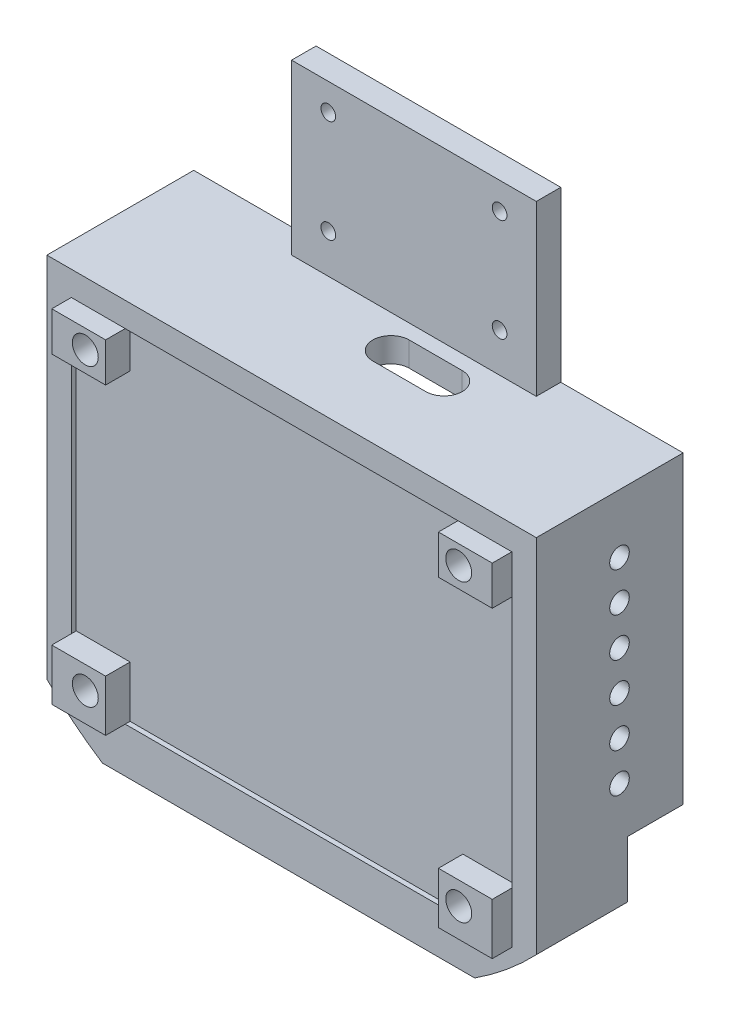
SolidWorks part; units mm, degrees
material "PLA"
ref_plane "Plano frontal" through (0, 0, 0) normal (0, 0, 1) x (1, 0, 0)
ref_plane "Plano superior" through (0, 0, 0) normal (0, 1, 0) x (1, 0, 0)
ref_plane "Plano direito" through (0, 0, 0) normal (1, 0, 0) x (0, 0, -1)
other "pla"
sketch "Esboço1" plane through (0, 0, 0) normal (0, 0, 1) x (1, 0, 0)
  line L6 (-49.3816, -49.6131) -> (-49.3816, 49.6131)
  line L8 (50.6184, -48.3506) -> (50.6184, 48.3506)
  arc A0 (-49.3816, -49.6131) -> (50.6184, -48.3506) centre (0, 0) ccw
  arc A1 (50.6184, 48.3506) -> (-49.3816, 49.6131) centre (0, 0) ccw
  point P0 (0, 0)
  dimension "D1" = 100
extrude "Ressalto-extrusão1" add sketch "Esboço1" along normal blind 30
sketch "Esboço10" plane through (0, 0, 30) normal (0, 0, 1) x (1, 0, 0)
  line L1 (-56.0991, 25.4453) -> (56.0991, 25.4453)
  line L2 (-56.0991, 25.4453) -> (-56.0991, 73.7415)
  line L3 (-56.0991, 73.7415) -> (56.0991, 73.7415)
  line L4 (56.0991, 25.4453) -> (56.0991, 73.7415)
  line L5 (-56.0991, 25.4453) -> (56.0991, 73.7415) construction
  line L6 (-56.0991, 73.7415) -> (56.0991, 25.4453) construction
  point P0 (0, 49.5934)
extrude "Corte-extrusão6" cut sketch "Esboço10" against normal blind 25
sketch "Esboço12" plane through (0, 0, 5) normal (0, 0, 1) x (1, 0, 0)
  line L0 (-24.3816, 25.4453) -> (-24.3816, 72.1449)
  line L1 (-49.3816, 25.4453) -> (50.6184, 25.4453) construction
  line L3 (25.6184, 72.1449) -> (25.6184, 25.4453)
  line L5 (50.6184, 48.3506) -> (50.6184, 25.4453) construction
  line L6 (-49.3816, 25.4453) -> (-49.3816, 49.6131) construction
  line L7 (-38.033, -58.7664) -> (38.033, -58.7664)
  line L8 (38.033, -58.7664) -> (38.033, -75.3889)
  line L9 (38.033, -75.3889) -> (-38.033, -75.3889)
  line L10 (-38.033, -75.3889) -> (-38.033, -58.7664)
  line L11 (-24.3816, 72.1449) -> (-61.1056, 72.1449)
  line L12 (-61.1056, 72.1449) -> (-61.1056, 25.4453)
  line L13 (-61.1056, 25.4453) -> (-24.3816, 25.4453)
  line L14 (25.6184, 72.1449) -> (62.1417, 72.1449)
  line L15 (62.1417, 72.1449) -> (62.1417, 25.4453)
  line L16 (62.1417, 25.4453) -> (25.6184, 25.4453)
  arc A0 (-49.3816, -49.6131) -> (50.6184, -48.3506) centre (0, 0) ccw construction
  point P8 (50.6184, 36.8979)
  dimension "D1" = 25
  dimension "D2" = 25
extrude "Corte-extrusão7" cut sketch "Esboço12" along normal through all both and the other way through all
sketch "Esboço13" plane through (0, 0, 0) normal (0, 0, -1) x (-1, 0, 0)
  line L0 (49.3816, 25.4453) -> (24.3816, 25.4453) construction
  line L1 (-18.1184, -34.5547) -> (16.8816, -34.5547)
  line L2 (-18.1184, -34.5547) -> (-18.1184, 20.4453)
  line L3 (-18.1184, 20.4453) -> (16.8816, 20.4453)
  line L4 (16.8816, -34.5547) -> (16.8816, 20.4453)
  line L5 (-18.1184, -34.5547) -> (16.8816, 20.4453) construction
  line L6 (-18.1184, 20.4453) -> (16.8816, -34.5547) construction
  line L7 (-50.6184, -48.3506) -> (-50.6184, 25.4453) construction
  line L8 (-25.6184, 65.1437) -> (-25.6184, 25.4453) construction
  line L9 (24.3816, 25.4453) -> (24.3816, 65.6166) construction
  line L10 (49.3816, 25.4453) -> (49.3816, -49.6131) construction
  line L11 (-0.6621, 69.9969) -> (-0.6621, -51.244) construction
  arc A0 (24.3816, 65.6166) -> (-25.6184, 65.1437) centre (0, 0) ccw construction
  point P0 (0, 0)
  dimension "D1" = 5
  dimension "D2" = 32.5
  dimension "D3" = 25
  dimension "D4" = 50
  dimension "D5" = 25
  dimension "D6" = 35
  dimension "D7" = 55
extrude "Corte-extrusão8" cut sketch "Esboço13" against normal blind 20
sketch "Esboço14" plane through (0, 25.4453, 0) normal (0, 1, 0) x (1, 0, 0)
  line L8 (2.6531, -11.7201) -> (13.483, -11.7201) construction
  line L9 (2.6531, -7.9985) -> (13.483, -7.9985)
  line L10 (2.6531, -15.4418) -> (13.483, -15.4418)
  arc A0 (2.6531, -7.9985) -> (2.6531, -15.4418) centre (2.6531, -11.7201) ccw
  arc A1 (13.483, -15.4418) -> (13.483, -7.9985) centre (13.483, -11.7201) ccw
  point P0 (0.6184, -11.7201)
  point P11 (8.0681, -11.7201)
extrude "Corte-extrusão9" cut sketch "Esboço14" against normal blind 20
sketch "Esboço15" plane through (0, 0, 30) normal (0, 0, 1) x (1, 0, 0)
  line L0 (50.6184, -48.3506) -> (50.6184, 25.4453) construction
  line L1 (-44.3816, -49.5547) -> (45.6184, -49.5547)
  line L2 (-44.3816, -49.5547) -> (-44.3816, 20.4453)
  line L3 (-44.3816, 20.4453) -> (45.6184, 20.4453)
  line L4 (45.6184, -49.5547) -> (45.6184, 20.4453)
  line L5 (-44.3816, -49.5547) -> (45.6184, 20.4453) construction
  line L6 (-44.3816, 20.4453) -> (45.6184, -49.5547) construction
  line L7 (-49.3816, 25.4453) -> (50.6184, 25.4453) construction
  point P0 (0.6184, -14.5547)
  dimension "D1" = 5
  dimension "D2" = 5
extrude "Corte-extrusão10" cut sketch "Esboço15" against normal blind 1
sketch "Esboço16" plane through (0, 0, 0) normal (0, 0, -1) x (-1, 0, 0)
  line L0 (-45.6184, 20.4453) -> (-45.6184, -34.5547)
  line L4 (44.3816, -34.5547) -> (44.3816, 20.4453)
  line L5 (44.3816, 20.4453) -> (21.8816, 20.4453)
  line L6 (-45.6184, 20.4453) -> (44.3816, 20.4453) construction
  line L7 (21.8816, 20.4453) -> (21.8816, -34.5547)
  line L9 (-23.1184, -34.5547) -> (-23.1184, 20.4453)
  line L10 (-45.6184, 20.4453) -> (-23.1184, 20.4453)
  line L11 (-18.1184, 20.4453) -> (-18.1184, -34.5547) construction
  line L12 (16.8816, -34.5547) -> (16.8816, 20.4453) construction
  line L14 (-23.1184, -34.5547) -> (-45.6184, -34.5547)
  line L15 (21.8816, -34.5547) -> (44.3816, -34.5547)
  dimension "D1" = 5
  dimension "D2" = 5
extrude "Corte-extrusão11" cut sketch "Esboço16" against normal blind 25
sketch "Esboço18" plane through (0, 0, 0) normal (0, 0, -1) x (-1, 0, 0)
  line L0 (-45.6184, 20.4453) -> (44.3816, 20.4453)
  line L1 (44.3816, 20.4453) -> (44.3816, -34.5547)
  line L2 (44.3816, -34.5547) -> (-45.6184, -34.5547)
  line L3 (-45.6184, -34.5547) -> (-45.6184, 20.4453)
  line L4 (-42.8719, -34.5547) -> (65.7902, -34.5547) construction
  line L5 (-45.6184, -34.5547) -> (-23.1184, -34.5547) construction
extrude "Ressalto-extrusão2" add sketch "Esboço18" against normal blind 3
sketch "Esboço19" plane through (0, 0, 0) normal (0, 0, -1) x (-1, 0, 0)
  line L0 (-50.6184, -48.3506) -> (-50.6184, 25.4453) construction
  line L1 (-18.1184, 20.4453) -> (16.8816, 20.4453)
  line L2 (-18.1184, 20.4453) -> (-18.1184, -34.5547)
  line L3 (-18.1184, -34.5547) -> (16.8816, -34.5547)
  line L4 (16.8816, 20.4453) -> (16.8816, -34.5547)
  line L5 (49.3816, 25.4453) -> (24.3816, 25.4453) construction
  dimension "D1" = 32.5
  dimension "D2" = 5
  dimension "D3" = 55
extrude "Corte-extrusão12" cut sketch "Esboço19" against normal blind 3
sketch "Esboço20" plane through (50.6184, 0, 0) normal (1, 0, 0) x (0, 0, -1)
  line L0 (0, -48.3506) -> (0, 25.4453) construction
  line L1 (0, 25.4453) -> (-30, 25.4453) construction
  circle A0 centre (-13, 5.4453) radius 2
  circle A1 centre (-13, -2.5547) radius 2
  circle A2 centre (-13, 13.4453) radius 2
  circle A3 centre (-13, -10.5547) radius 2
  circle A4 centre (-13, -18.5547) radius 2
  circle A5 centre (-13, -26.5547) radius 2
  dimension "D2" = 8
  dimension "D7" = 12
  dimension "D1" = 13
  dimension "D3" = 8
  dimension "D4" = 8
  dimension "D5" = 8
  dimension "D6" = 8
extrude "Corte-extrusão13" cut sketch "Esboço20" against normal blind 1500
sketch "Esboço21" plane through (0, 0, 0) normal (0, 0, -1) x (-1, 0, 0)
  line L0 (-50.6184, -48.3506) -> (-50.6184, 25.4453) construction
  line L1 (-50.6184, -36.7664) -> (54.9698, -36.7664)
  line L2 (-50.6184, -36.7664) -> (-50.6184, -65.1203)
  line L3 (-50.6184, -65.1203) -> (54.9698, -65.1203)
  line L4 (54.9698, -36.7664) -> (54.9698, -65.1203)
  line L5 (-38.033, -58.7664) -> (38.033, -58.7664) construction
  dimension "D1" = 22
extrude "Corte-extrusão14" cut sketch "Esboço21" against normal blind 11.4
sketch "Esboço22" plane through (0, 0, 5) normal (0, 0, 1) x (1, 0, 0)
  line L1 (-29.9805, 70.9453) -> (31.25, 70.9422)
  line L2 (-29.9805, 70.9453) -> (-29.9805, 59.9453)
  line L3 (-29.9805, 59.9453) -> (31.25, 59.9453)
  line L4 (31.25, 59.9453) -> (31.25, 70.9422)
  line L5 (-24.3816, 25.4453) -> (25.6184, 25.4453) construction
  dimension "D1" = 34.5
  dimension "D2" = 11
extrude "Corte-extrusão15" cut sketch "Esboço22" against normal blind 10
sketch "Esboço23" plane through (0, 0, 5) normal (0, 0, 1) x (1, 0, 0)
  line L0 (-24.3816, 59.9453) -> (25.6184, 59.9453) construction
  line L1 (0.6184, 59.9453) -> (0.6184, 16.8032) construction
  line L2 (-24.3816, 25.4453) -> (-24.3816, 59.9453) construction
  circle A0 centre (-16.8816, 54.4453) radius 1.5
  circle A1 centre (-16.8816, 33.4453) radius 1.5
  circle A2 centre (18.1184, 33.4453) radius 1.5
  circle A3 centre (18.1184, 54.4453) radius 1.5
  dimension "D1" = 5.5
  dimension "D2" = 26.5
  dimension "D3" = 7.5
  dimension "D4" = 7.5
extrude "Corte-extrusão16" cut sketch "Esboço23" against normal blind 6
sketch "Esboço29" plane through (0, 0, 0) normal (0, 0, -1) x (-1, 0, 0)
  line L0 (-18.1184, 7.9453) -> (-25.1184, 7.9453)
  line L1 (-18.1184, 20.4453) -> (-18.1184, -34.5547) construction
  line L2 (-25.1184, 7.9453) -> (-25.1184, -22.0547)
  line L3 (-25.1184, -22.0547) -> (-18.1184, -22.0547)
  line L4 (-18.1184, -22.0547) -> (-18.1184, 7.9453)
  line L5 (16.8816, -7.0547) -> (-31.051, -7.0547) construction
  line L6 (16.8816, -34.5547) -> (16.8816, 20.4453) construction
  point P10 (-25.1184, -7.0547)
extrude "Corte-extrusão18" cut sketch "Esboço29" against normal blind 1.2
sketch "Esboço31" plane through (18.1184, 0, 0) normal (-1, 0, 0) x (0, 0, 1)
  line L0 (1.2, 12.6884) -> (1.2, 16.6884)
  line L1 (1.2, 12.6884) -> (3.5, 12.6884)
  line L2 (3.5, 12.6884) -> (3.5, 16.6884)
  line L3 (3.5, 16.6884) -> (1.2, 16.6884)
  line L4 (0, -7.0547) -> (41.9938, -7.0547) construction
  line L5 (0, 7.9453) -> (0, -22.0547) construction
  line L6 (1.2, -26.7978) -> (3.5, -26.7978)
  line L7 (3.5, -26.7978) -> (3.5, -30.7978)
  line L8 (3.5, -30.7978) -> (1.2, -30.7978)
  line L9 (1.2, -26.7978) -> (1.2, -30.7978)
  line L10 (1.2, 7.2672) -> (1.2, 17.4313) construction
  line L11 (1.2, -22.0547) -> (1.2, 7.9453) construction
extrude "Corte-extrusão19" cut sketch "Esboço31" against normal blind 4
sketch "Esboço33" plane through (-16.8816, 0, 0) normal (1, 0, 0) x (0, 0, -1)
  line L0 (-2.5, -3.7234) -> (-2.5, -9.7234)
  line L1 (-2.5, -9.7234) -> (-1.5, -9.7234)
  line L4 (-1.5, -3.7234) -> (-2.5, -3.7234)
  line L6 (-1.5, -3.7234) -> (-1.5, -9.7234)
  line L7 (0, -36.7664) -> (0, 25.4453) construction
  dimension "D1" = 1.5
extrude "Corte-extrusão20" cut sketch "Esboço33" against normal blind 4
sketch "Esboço34" plane through (0, 0, 11.4) normal (0, 0, -1) x (-1, 0, 0)
  line L0 (-50.6184, -49.3664) -> (49.3816, -49.3664) construction
  line L1 (-50.6184, -36.7664) -> (-50.6184, -48.3506) construction
  line L2 (49.3816, -49.6131) -> (49.3816, -36.7664) construction
  line L3 (49.3816, -36.7664) -> (-50.6184, -36.7664) construction
  line L4 (0, 3.7247) -> (0, -70.0646) construction
  circle A0 centre (20, -49.3664) radius 2.5
  circle A1 centre (-20, -49.3664) radius 2.5
  dimension "D2" = 20
  dimension "D3" = 20
  dimension "D1" = 12.6
extrude "Corte-extrusão21" cut sketch "Esboço34" against normal blind 6
sketch "Esboço35" plane through (0, 0, 29) normal (0, 0, 1) x (1, 0, 0)
  line L1 (-44.3816, 20.4453) -> (-33.3816, 20.4453)
  line L2 (-44.3816, 20.4453) -> (-44.3816, 12.4453)
  line L3 (-44.3816, 12.4453) -> (-33.3816, 12.4453)
  line L4 (-33.3816, 20.4453) -> (-33.3816, 12.4453)
  line L5 (45.6184, 20.4453) -> (34.6184, 20.4453)
  line L6 (45.6184, 20.4453) -> (45.6184, 12.4453)
  line L7 (45.6184, 12.4453) -> (34.6184, 12.4453)
  line L8 (34.6184, 20.4453) -> (34.6184, 12.4453)
  line L9 (45.6184, -49.5547) -> (34.6184, -49.5547)
  line L10 (45.6184, -49.5547) -> (45.6184, -39.0547)
  line L11 (45.6184, -39.0547) -> (34.6184, -39.0547)
  line L12 (34.6184, -49.5547) -> (34.6184, -39.0547)
  line L13 (-44.3816, -49.5547) -> (-33.3816, -49.5547)
  line L14 (-44.3816, -49.5547) -> (-44.3816, -39.0547)
  line L15 (-44.3816, -39.0547) -> (-33.3816, -39.0547)
  line L16 (-33.3816, -49.5547) -> (-33.3816, -39.0547)
  dimension "D1" = 11
  dimension "D2" = 11
  dimension "D3" = 11
  dimension "D4" = 11
  dimension "D5" = 8
  dimension "D6" = 8
  dimension "D7" = 10.5
  dimension "D8" = 10.5
extrude "Ressalto-extrusão3" add sketch "Esboço35" along normal blind 5
sketch "Esboço36" plane through (0, 0, 34) normal (0, 0, 1) x (1, 0, 0)
  line L0 (45.6184, -49.5547) -> (45.6184, -39.0547) construction
  line L1 (-44.3816, 20.4453) -> (-44.3816, 12.4453) construction
  line L2 (-33.3816, 20.4453) -> (-44.3816, 20.4453) construction
  line L3 (45.6184, 20.4453) -> (34.6184, 20.4453) construction
  line L4 (-44.3816, -49.5547) -> (-33.3816, -49.5547) construction
  line L5 (45.6184, 12.4453) -> (45.6184, 20.4453) construction
  line L6 (34.6184, -49.5547) -> (45.6184, -49.5547) construction
  line L7 (-44.3816, -39.0547) -> (-44.3816, -49.5547) construction
  circle A0 centre (-37.5316, 16.5953) radius 2.65
  circle A1 centre (38.7684, 16.5953) radius 2.65
  circle A2 centre (38.7684, -43.7047) radius 2.65
  circle A3 centre (-37.5316, -43.7047) radius 2.65
  dimension "D1" = 6.85
  dimension "D2" = 3.85
  dimension "D3" = 3.85
  dimension "D5" = 6.85
  dimension "D7" = 5.85
  dimension "D4" = 6.85
  dimension "D6" = 5.85
  dimension "D8" = 6.85
extrude "Corte-extrusão22" cut sketch "Esboço36" against normal blind 4.7
sketch "Esboço38" plane through (0, 0, 0) normal (0, 0, -1) x (-1, 0, 0)
  line L0 (16.8816, -7.0547) -> (-43.1425, -7.0547) construction
  line L1 (-18.1184, 21.4453) -> (17.8816, 21.4453)
  line L2 (-18.1184, 21.4453) -> (-18.1184, -35.5547)
  line L3 (-18.1184, -35.5547) -> (17.8816, -35.5547)
  line L4 (17.8816, 21.4453) -> (17.8816, -35.5547)
  line L5 (16.8816, -34.5547) -> (16.8816, 20.4453) construction
  line L7 (-18.1184, 20.4453) -> (-18.1184, 7.9453) construction
  point P8 (-18.1184, -7.0547)
extrude "Corte-extrusão23" cut sketch "Esboço38" against normal blind 1.2
fillet "Filete4" radius 1 1 edges at (-17.8816, 21.4453, 0.6)
fillet "Filete5" radius 1 3 edges at (18.1184, -35.5547, 0.6) (-17.8816, -35.5547, 0.6) (18.1184, 21.4453, 0.6)
fillet "Filete6" radius 1 2 edges at (25.1184, -22.0547, 0.6) (25.1184, 7.9453, 0.6)
sketch "Esboço39" plane through (0, 0, 0) normal (0, 0, -1) x (-1, 0, 0)
  line L0 (-22.6184, 4.6735) -> (-22.6184, -18.7829) construction
  line L1 (-25.1184, 6.9453) -> (-25.1184, -21.0547) construction
  line L2 (-25.1184, -7.0547) -> (-15.6833, -7.0547) construction
  line L3 (-25.1184, 6.9453) -> (-25.1184, -21.0547) construction
  circle A0 centre (-22.6184, -7.0547) radius 4.5
  point P8 (-22.6184, -7.0547)
  dimension "D1" = 2.5
sketch "Esboço40" plane through (0, 0, 0) normal (0, 0, -1) x (-1, 0, 0)
  line L0 (16.8816, -3.7234) -> (16.8816, -9.7234) construction
  circle A0 centre (16.8816, -6.7234) radius 4.0367
extrude "Corte-extrusão25" cut sketch "Esboço40" against normal blind 1
fillet "Filete9" radius 4 1 edges at (-20.9183, -6.7234, 1)
